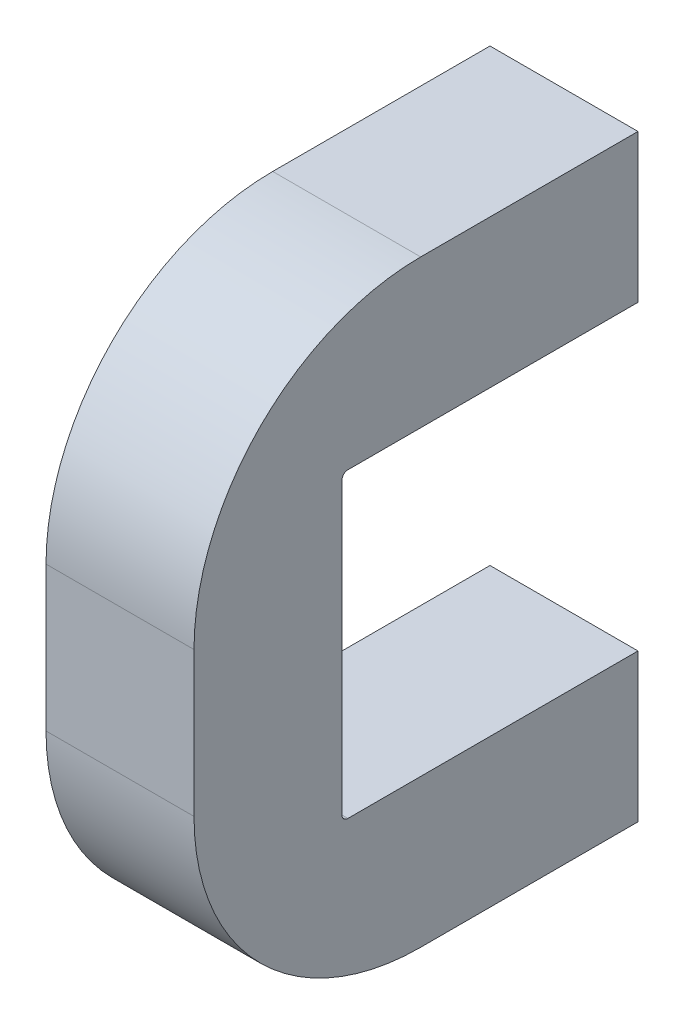
SolidWorks part; units mm, degrees
ref_plane "Alzado" through (0, 0, 0) normal (0, 0, 1) x (1, 0, 0)
ref_plane "Planta" through (0, 0, 0) normal (0, 1, 0) x (1, 0, 0)
ref_plane "Vista lateral" through (0, 0, 0) normal (1, 0, 0) x (0, 0, -1)
sketch "Croquis2" plane through (-2.5254, 2.1233, -2.4669) normal (1, 0, 0) x (0, 0, -1)
  line L0 (123.1989, 153.4478) -> (118.2817, 153.4478) construction
  line L1 (123.3989, 158.565) -> (123.3989, 153.6478) construction
  line L2 (108.516, 153.4478) -> (103.5989, 153.4478) construction
  line L3 (103.3989, 153.6478) -> (103.3989, 158.565) construction
  line L4 (123.3989, 173.2478) -> (123.3989, 168.3306) construction
  line L5 (118.2817, 173.4478) -> (123.1989, 173.4478) construction
  line L6 (103.3989, 168.3306) -> (103.3989, 173.2478) construction
  line L7 (103.5989, 173.4478) -> (108.516, 173.4478) construction
  line L8 (123.1989, 153.4478) -> (118.2817, 153.4478) construction
  line L9 (123.3989, 158.565) -> (123.3989, 153.6478) construction
  line L10 (108.516, 153.4478) -> (103.5989, 153.4478) construction
  line L11 (103.3989, 153.6478) -> (103.3989, 158.565) construction
  line L12 (123.3989, 173.2478) -> (123.3989, 168.3306) construction
  line L13 (118.2817, 173.4478) -> (123.1989, 173.4478) construction
  line L14 (103.3989, 168.3306) -> (103.3989, 173.2478) construction
  line L15 (103.5989, 173.4478) -> (108.516, 173.4478) construction
  line L16 (108.516, 173.4478) -> (118.2817, 173.4478) construction
  line L17 (103.3989, 168.3306) -> (103.3989, 158.565) construction
  line L18 (123.3989, 168.3306) -> (123.3989, 158.565) construction
  line L19 (108.516, 153.4478) -> (118.2817, 153.4478) construction
  line L20 (108.516, 173.6478) -> (118.2817, 173.6478)
  line L21 (118.2817, 173.6478) -> (123.1989, 173.6478)
  line L22 (123.5989, 173.2478) -> (123.5989, 168.3306)
  line L25 (123.1989, 153.2478) -> (118.2817, 153.2478)
  line L26 (108.516, 153.2478) -> (118.2817, 153.2478)
  line L27 (108.516, 153.2478) -> (103.5989, 153.2478)
  line L28 (103.1989, 153.6478) -> (103.1989, 158.565)
  line L29 (103.1989, 168.3306) -> (103.1989, 158.565)
  line L30 (103.1989, 168.3306) -> (103.1989, 173.2478)
  line L31 (103.5989, 173.6478) -> (108.516, 173.6478)
  line L32 (108.516, 143.2478) -> (118.2817, 143.2478)
  line L33 (93.1989, 168.3306) -> (93.1989, 158.565)
  line L34 (108.516, 183.6478) -> (118.2817, 183.6478)
  line L35 (124.3989, 167.5306) -> (124.3989, 159.365)
  line L36 (124.3989, 167.5306) -> (124.3989, 183.6478)
  line L37 (118.2817, 183.6478) -> (124.3989, 183.6478)
  line L38 (124.3989, 159.365) -> (124.3989, 143.2478)
  line L39 (118.2817, 143.2478) -> (124.3989, 143.2478)
  line L40 (123.1989, 173.6478) -> (124.3989, 173.6478)
  line L41 (123.5989, 168.3306) -> (123.5989, 158.565) construction
  line L42 (123.5989, 158.565) -> (123.5989, 153.6478) construction
  line L43 (123.1989, 153.2478) -> (124.3989, 153.2478)
  line L44 (123.1989, 154.2478) -> (124.3989, 154.2478)
  line L45 (123.1989, 154.2478) -> (118.2817, 154.2478)
  line L46 (108.516, 154.2478) -> (118.2817, 154.2478)
  line L47 (108.516, 154.2478) -> (104.1989, 154.2478)
  line L48 (104.1989, 154.2478) -> (104.1989, 158.565)
  line L49 (104.1989, 168.3306) -> (104.1989, 158.565)
  line L50 (104.1989, 168.3306) -> (104.1989, 172.6478)
  line L51 (104.1989, 172.6478) -> (108.516, 172.6478)
  line L52 (108.516, 172.6478) -> (118.2817, 172.6478)
  line L53 (118.2817, 172.6478) -> (123.1989, 172.6478)
  line L54 (123.1989, 172.6478) -> (124.3989, 172.6478)
  line L55 (123.1989, 173.4478) -> (124.3989, 172.6478)
  line L56 (123.1989, 153.4478) -> (124.3989, 154.2478)
  line L57 (123.1989, 172.6478) -> (123.1989, 183.6478)
  line L58 (123.1989, 154.2478) -> (123.1989, 143.2478)
  arc A0 (123.1989, 153.4478) -> (123.3989, 153.6478) centre (123.1989, 153.6478) ccw construction
  arc A1 (103.3989, 153.6478) -> (103.5989, 153.4478) centre (103.5989, 153.6478) ccw construction
  arc A2 (123.3989, 173.2478) -> (123.1989, 173.4478) centre (123.1989, 173.2478) ccw construction
  arc A3 (103.5989, 173.4478) -> (103.3989, 173.2478) centre (103.5989, 173.2478) ccw construction
  arc A4 (123.1989, 153.4478) -> (123.3989, 153.6478) centre (123.1989, 153.6478) ccw construction
  arc A5 (103.3989, 153.6478) -> (103.5989, 153.4478) centre (103.5989, 153.6478) ccw construction
  arc A6 (123.3989, 173.2478) -> (123.1989, 173.4478) centre (123.1989, 173.2478) ccw construction
  arc A7 (103.5989, 173.4478) -> (103.3989, 173.2478) centre (103.5989, 173.2478) ccw construction
  arc A10 (103.1989, 153.6478) -> (103.5989, 153.2478) centre (103.5989, 153.6478) ccw
  arc A11 (103.5989, 173.6478) -> (103.1989, 173.2478) centre (103.5989, 173.2478) ccw
  arc A12 (108.516, 183.6478) -> (93.1989, 168.3306) centre (108.516, 168.3306) ccw
  arc A13 (93.1989, 158.565) -> (108.516, 143.2478) centre (108.516, 158.565) ccw
  arc A14 (104.1989, 154.2478) -> (104.1989, 154.2478) centre (104.1989, 154.2478) ccw
  arc A15 (123.1989, 153.2478) -> (123.5989, 153.6478) centre (123.1989, 153.6478) ccw construction
  arc A16 (123.5989, 173.2478) -> (123.1989, 173.6478) centre (123.1989, 173.2478) ccw construction
  arc A17 (104.1989, 172.6478) -> (104.1989, 172.6478) centre (104.1989, 172.6478) ccw
  dimension "D1" = 0.2
  dimension "D2" = 10
  dimension "D3" = 10
  dimension "D4" = 10
  dimension "D5" = 1
extrude "Saliente-Extruir1" add sketch "Croquis2" along normal blind 10 contours L33 A13 L32 L39 L38 L43 L25 L26 L27 A10 L28 L29 L30 A11 L31 L20 L21 L40 L36 L37 L34 A12 region at (-2.5254, 176.2743, -108.5243)
sketch "Croquis3" plane through (0, 0, -126.8658) normal (0, 0, -1) x (-1, 0, 0)
  line L0 (2.5254, 175.7711) -> (2.5254, 185.7711) construction
  line L17 (2.5254, 185.7711) -> (-7.4746, 185.7711) construction
  line L18 (-7.4746, 185.7711) -> (-7.4746, 175.7711) construction
  line L19 (-7.4746, 175.7711) -> (2.5254, 175.7711) construction
  line L20 (2.5254, 145.3711) -> (2.5254, 155.3711) construction
  line L25 (2.5254, 155.3711) -> (-7.4746, 155.3711) construction
  line L30 (-7.4746, 155.3711) -> (-7.4746, 145.3711) construction
  line L31 (-7.4746, 145.3711) -> (2.5254, 145.3711) construction
  line L32 (2.5254, 175.7711) -> (2.5254, 185.7711)
  line L33 (2.5254, 185.7711) -> (-7.4746, 185.7711)
  line L34 (-7.4746, 185.7711) -> (-7.4746, 175.7711)
  line L35 (-7.4746, 175.7711) -> (2.5254, 175.7711)
  line L36 (2.5254, 145.3711) -> (2.5254, 155.3711)
  line L37 (2.5254, 155.3711) -> (-7.4746, 155.3711)
  line L38 (-7.4746, 155.3711) -> (-7.4746, 145.3711)
  line L39 (-7.4746, 145.3711) -> (2.5254, 145.3711)
  line L40 (-7.4746, 175.7711) -> (2.5254, 185.7711)
  line L41 (-7.4746, 185.7711) -> (2.5254, 175.7711)
  line L42 (2.5254, 155.3711) -> (-7.4746, 145.3711)
  line L43 (-7.4746, 155.3711) -> (2.5254, 145.3711)
  circle A2 centre (-2.4746, 150.3711) radius 3.1
  circle A3 centre (-2.4746, 180.7711) radius 3.1
  circle A4 centre (-5.5746, 180.7711) radius 1.25
  circle A5 centre (-5.5746, 150.3711) radius 1.25
  dimension "D2" = 2.5
  dimension "D1" = 6.2
extrude "Cortar-Extruir1" cut sketch "Croquis3" against normal blind 4 contours L42 A2 L43 | A5 A2 L42 L43 | L42 A2 L43 | L43 A2 L42 | A2 A5 | A3 A4 | A3 A4 | A4 A3 L40 L41 | L40 A3 L41 | L40 A3 L41 | L41 A3 L40 | A2 region at (2.4746, 178.9104, -126.8658) region at (0.614, 180.7711, -126.8658) region at (2.4746, 182.6317, -126.8658) region at (4.0536, 180.7711, -126.8658) region at (6.0572, 180.7711, -126.8658) region at (5.0014, 180.7711, -126.8658) region at (2.4746, 148.5104, -126.8658) region at (0.614, 150.3711, -126.8658) region at (2.4746, 152.2317, -126.8658) region at (4.0536, 150.3711, -126.8658) region at (6.0572, 150.3711, -126.8658)
fillet "Redondeo2" radius 1.5 4 edges at (5.3226, 181.9954, -124.2658) (5.3226, 179.5468, -124.2658) (5.3226, 151.5954, -124.2658) (5.3226, 149.1468, -124.2658)
